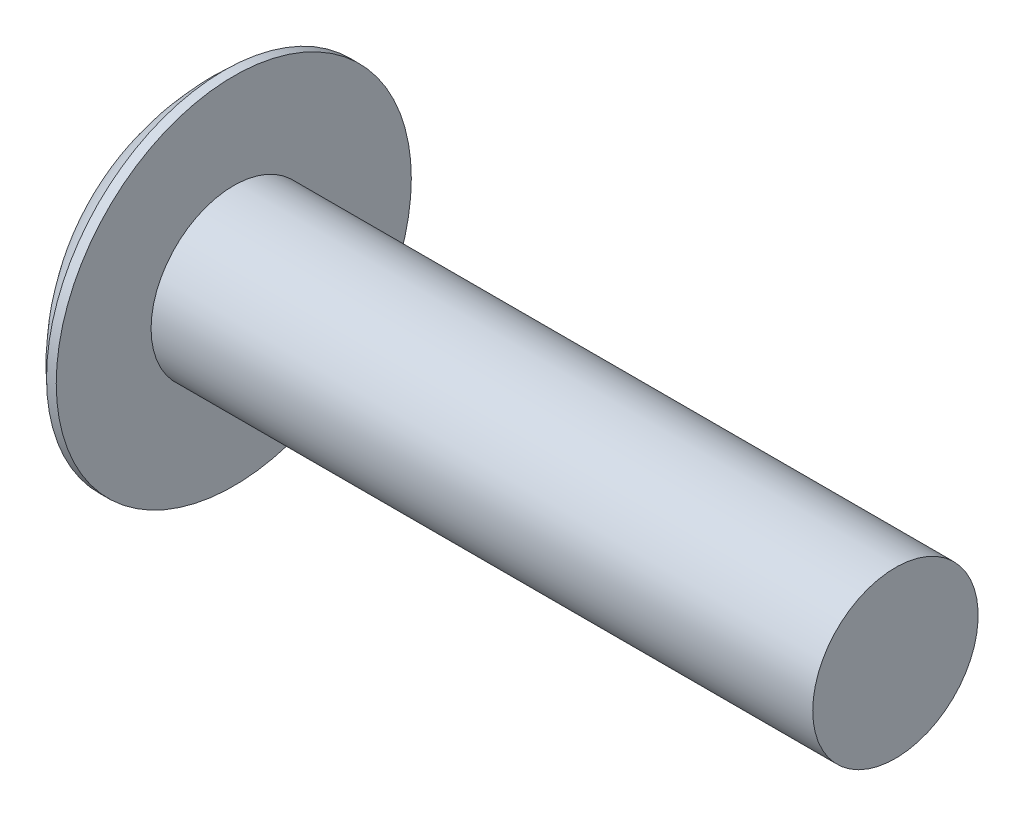
SolidWorks part; units mm, degrees
ref_plane "Plane1" through (0, 0, 0) normal (0, 0, 1) x (1, 0, 0)
ref_plane "Plane2" through (0, 0, 0) normal (0, 1, 0) x (1, 0, 0)
ref_plane "Plane3" through (0, 0, 0) normal (1, 0, 0) x (0, 0, -1)
sketch "BodySke" plane through (0, 0, 0) normal (0, 0, 1) x (1, 0, 0)
  line L0 (5.1562, 4.7625) -> (5.1562, 10.2235)
  line L1 (43.2562, 0) -> (0, 0)
  line L2 (-25.4, 0) -> (127, 0) construction
  line L3 (4.5978, -10.2235) -> (5.1562, -10.2235) construction
  line L4 (5.1562, 4.7625) -> (43.2562, 4.7625)
  line L5 (43.2562, 4.7625) -> (43.2562, 0)
  line L6 (4.5978, 10.2235) -> (5.1562, 10.2235)
  line L7 (5.1562, -4.7625) -> (43.2562, -4.7625) construction
  line L8 (6.7437, 6.35) -> (6.7437, -3.175) construction
  line L9 (11.5062, 6.35) -> (11.5062, -3.175) construction
  arc A0 (4.5978, 10.2235) -> (0, 0) centre (13.6652, 0) ccw
  dimension "Length" = 38.1
  dimension "Head_ht" = 5.1562
  dimension "Head_dia" = 20.447
  dimension "Diameter" = 9.525
  dimension "Advance" = 1.5875
revolve "Base-Revolve" add sketch "BodySke" angle 360 about L2
cosmetic thread "ThreadCosmetic" [suppressed] parameters "Thread_length"=31.75, "Thread_minor"=7.9375
sketch "Sketch2" plane through (0, 0, 0) normal (1, 0, 0) x (0, 0, -1)
  line L0 (10.2235, -1.1049) -> (-10.2235, -1.1049)
  line L1 (10.2235, -1.1049) -> (10.2235, 1.1049)
  line L2 (-10.2235, 1.1049) -> (10.2235, 1.1049)
  line L3 (-10.2235, 1.1049) -> (-10.2235, -1.1049)
  dimension "D1" = 20.447
  dimension "D2" = 10.2235
  dimension "D3" = 1.1049
extrude "Slot" cut sketch "Sketch2" along normal blind 2.8448
sketch "Sketch3" plane through (0, 0, 0) normal (1, 0, 0) x (0, 0, -1)
  line L0 (1.2319, -7.4676) -> (-1.2319, -7.4676)
  line L1 (1.2319, -7.4676) -> (1.2319, 7.4676)
  line L2 (-1.2319, 7.4676) -> (1.2319, 7.4676)
  line L3 (-1.2319, 7.4676) -> (-1.2319, -7.4676)
  dimension "D1" = 1.2319
  dimension "D2" = 7.4676
ref_plane "Plane4" through (8.9916, 0, 0) normal (1, 0, 0) x (0, 0, -1)
sketch "Sketch4" plane through (8.9916, 0, 0) normal (1, 0, 0) x (0, 0, -1)
  line L0 (0.616, -0.616) -> (-0.616, -0.6159)
  line L1 (0.616, -0.616) -> (0.616, 0.616)
  line L2 (-0.616, 0.616) -> (0.616, 0.616)
  line L3 (-0.616, 0.616) -> (-0.616, -0.6159)
  dimension "D1" = 1.2319
  dimension "D2" = 0.6159
  dimension "D3" = 1.2319
  dimension "D4" = 0.6159
loft "Cross" cut profiles "Sketch3", "Sketch4"
pattern_circular "CirPattern1" count 2 every 90 about axis through (-25.4, 0, 0) along (1, 0, 0) of "Cross"
sketch "ThdSchSke" plane through (0, 0, 0) normal (0, 0, 1) x (1, 0, 0)
  line L0 (11.5062, -3.9688) -> (10.9504, -4.7625)
  line L1 (11.5062, -3.9688) -> (12.062, -4.7625)
  line L2 (12.062, -4.7625) -> (12.062, -5.9531)
  line L3 (-3.175, 0) -> (5.1513, 0) construction
  line L5 (12.062, -5.9531) -> (10.9504, -5.9531)
  line L6 (10.9504, -5.9531) -> (10.9504, -4.7625)
  dimension "Thread_minor" = 7.9375
  dimension "Diameter" = 9.525
  dimension "Start" = 11.5062
revolve "ThreadSchematic" [suppressed] cut sketch "ThdSchSke" angle 360 about L3
pattern_linear "ThdSchPat" [suppressed]
equation "\"D1@Sketch2\" = \"Head_dia@BodySke\""
equation "\"D2@Sketch2\" = \"D1@Sketch2\" / 2"
equation "\"D3@Sketch2\" = \"Slot_width@Sketch2\" / 2"
equation "\"D1@Sketch3\" = \"Cross_width@Sketch3\" / 2"
equation "\"D2@Sketch3\" = \"Cross_dia@Sketch3\" / 2"
equation "\"D1@Sketch4\" = \"Cross_width@Sketch3\" *.5"
equation "\"D2@Sketch4\" = \"D1@Sketch4\" / 2"
equation "\"D3@Sketch4\" = \"D1@Sketch4\""
equation "\"D4@Sketch4\" = \"D3@Sketch4\" / 2"
equation "\"Thread_length@ThreadCosmetic\" = ((sgn( (\"Length@BodySke\" - \"Advance@BodySke\" ) - \"Thread_nom@BodySke\" )-1)*( (\"Length@BodySke\" - \"Advance@BodySke\" ) - \"Thread_nom@BodySke\" ))/-2+ \"Thread_nom@BodySke\""
equation "\"Thread_minor@ThdSchSke\" = \"Thread_minor@ThreadCosmetic\""
equation "\"Diameter@ThdSchSke\" = \"Diameter@BodySke\""
equation "\"Overcut@ThdSchSke\" = \"Diameter@BodySke\" * 1.25"
equation "\"Start@ThdSchSke\" = \"Head_ht@BodySke\" + \"Length@BodySke\" - \"Thread_length@ThreadCosmetic\"  '---Non-countersunk---"
equation "\"Num_threads@ThdSchPat\" = int( \"Thread_length@ThreadCosmetic\" / \"Advance@BodySke\" + 0.999 )  + 1"
equation "\"Advance@ThdSchPat\" = \"Thread_length@ThreadCosmetic\" /  (\"Num_threads@ThdSchPat\" - 1) 'relax it"
